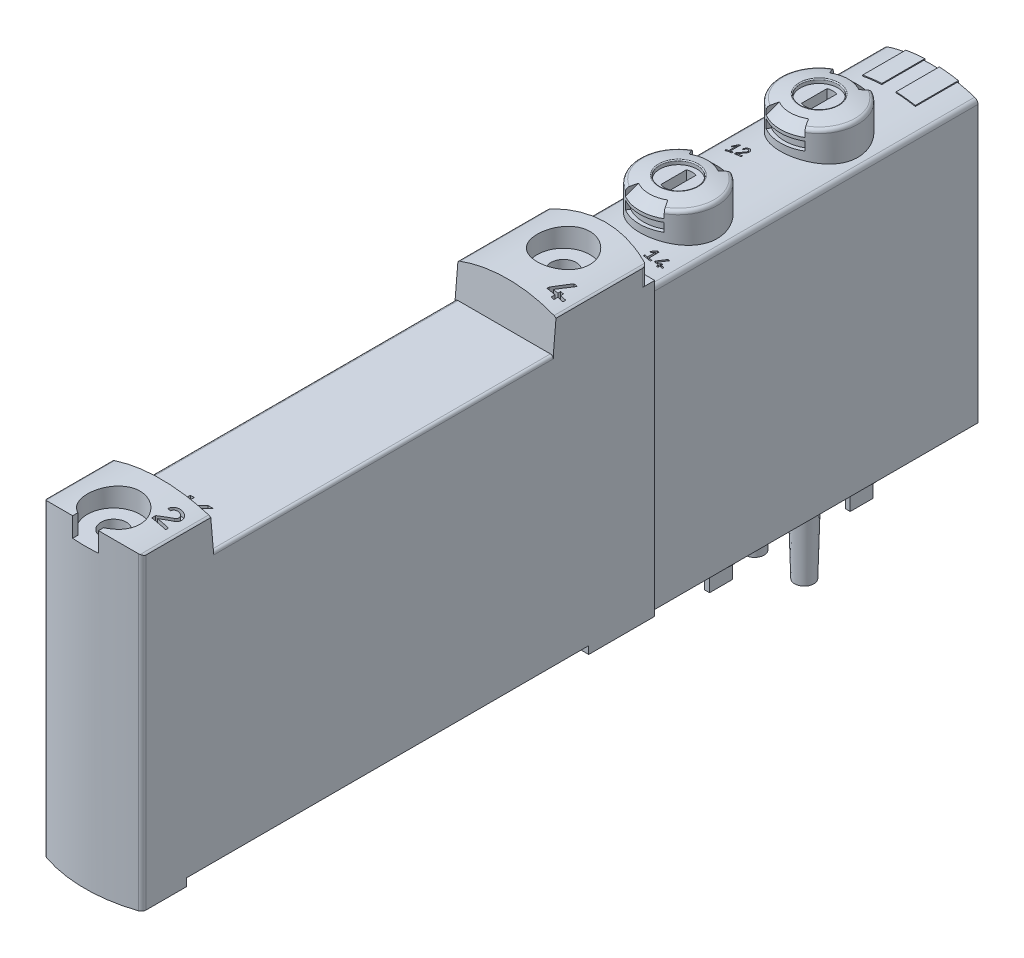
SolidWorks part; units mm, degrees
ref_plane "Front Plane" through (0, 0, 0) normal (0, 0, 1) x (1, 0, 0)
ref_plane "Top Plane" through (0, 0, 0) normal (0, 1, 0) x (1, 0, 0)
ref_plane "Right Plane" through (0, 0, 0) normal (1, 0, 0) x (0, 0, -1)
ref_plane "Plane1" through (0, 0, -23.2) normal (0, 0, 1) x (1, 0, 0)
sketch "Sketch1" plane through (0, 0, -23.2) normal (0, 0, 1) x (1, 0, 0)
  line L0 (-4.9, 29.2163) -> (-4.9, 0)
  line L1 (-4.9, 0) -> (4.9, 0)
  line L2 (4.9, 0) -> (4.9, 29.2163)
  arc A0 (4.9, 29.2163) -> (4.5517, 29.6927) centre (4.4, 29.2163) ccw
  arc A1 (4.5517, 29.6927) -> (-4.5517, 29.6927) centre (0, 15.4) ccw
  arc A2 (-4.5517, 29.6927) -> (-4.9, 29.2163) centre (-4.4, 29.2163) ccw
extrude "Boss-Extrude1" add sketch "Sketch1" along normal blind 34
ref_plane "Plane2" through (0, 0, 0) normal (1, 0, 0) x (0, 0, -1)
sketch "Sketch2" plane through (0, 0, 0) normal (1, 0, 0) x (0, 0, -1)
  line L0 (-10.88, 0.4) -> (-10.88, 0)
  line L1 (-10.88, 0) -> (23.22, 0)
  line L2 (23.22, 0) -> (23.22, 0.4)
  line L3 (23.22, 0.4) -> (-10.88, 0.4)
extrude "Cut-Extrude1" cut sketch "Sketch2" against normal blind 6 and the other way blind 6
ref_plane "Plane3" through (0, 0, 0) normal (0, 1, 0) x (1, 0, 0)
sketch "Sketch3" plane through (0, 0, 0) normal (0, 1, 0) x (1, 0, 0)
  line L0 (-3.15, 2.4653) -> (-3.15, -2.4653)
  line L1 (3.15, -2.4653) -> (3.15, 2.4653)
  arc A0 (-3.15, -2.4653) -> (3.15, -2.4653) centre (0, 0) ccw
  arc A1 (3.15, 2.4653) -> (-3.15, 2.4653) centre (0, 0) ccw
extrude "Cut-Extrude2" cut sketch "Sketch3" along normal blind 1.9
ref_plane "Plane4" through (0, 0, 0) normal (0, 1, 0) x (1, 0, 0)
sketch "Sketch4" plane through (0, 0, 0) normal (0, 1, 0) x (1, 0, 0)
  line L0 (-3.15, 17.1653) -> (-3.15, 12.2347)
  line L1 (3.15, 12.2347) -> (3.15, 17.1653)
  arc A0 (-3.15, 12.2347) -> (3.15, 12.2347) centre (0, 14.7) ccw
  arc A1 (3.15, 17.1653) -> (-3.15, 17.1653) centre (0, 14.7) ccw
extrude "Cut-Extrude3" cut sketch "Sketch4" along normal blind 1.9
ref_plane "Plane5" through (0, 0, 0) normal (1, 0, 0) x (0, 0, -1)
sketch "Sketch5" plane through (0, 0, 0) normal (1, 0, 0) x (0, 0, -1)
  line L0 (0, 2.1) -> (3.05, 2.1)
  line L1 (3.05, 2.1) -> (3.05, 1.1)
  line L2 (3.05, 1.1) -> (2.25, 1.1)
  line L3 (2.25, 1.1) -> (2.25, -1.4)
  line L4 (2.25, -1.4) -> (2.65, -1.4)
  line L5 (2.65, -1.4) -> (2.65, -1.72)
  line L6 (2.65, -1.72) -> (2.4306, -2.1)
  line L7 (2.4306, -2.1) -> (0, -2.1)
  line L8 (0, -2.1) -> (0, 2.1)
  line L9 (0, -2.1) -> (0, 2.1) construction
revolve "Revolve1" add sketch "Sketch5" angle 360 about L9 reverse direction yes
ref_plane "Plane6" through (0, 0, 0) normal (1, 0, 0) x (0, 0, -1)
sketch "Sketch6" plane through (0, 0, 0) normal (1, 0, 0) x (0, 0, -1)
  line L0 (14.7, 2.1) -> (17.75, 2.1)
  line L1 (17.75, 2.1) -> (17.75, 1.1)
  line L2 (17.75, 1.1) -> (16.95, 1.1)
  line L3 (16.95, 1.1) -> (16.95, -1.4)
  line L4 (16.95, -1.4) -> (17.35, -1.4)
  line L5 (17.35, -1.4) -> (17.35, -1.72)
  line L6 (17.35, -1.72) -> (17.1306, -2.1)
  line L7 (17.1306, -2.1) -> (14.7, -2.1)
  line L8 (14.7, -2.1) -> (14.7, 2.1)
  line L9 (14.7, -2.1) -> (14.7, 2.1) construction
revolve "Revolve2" add sketch "Sketch6" angle 360 about L9 reverse direction yes
ref_plane "Plane7" through (0, 0, -7.35) normal (0, 0, 1) x (1, 0, 0)
sketch "Sketch7" plane through (0, 0, -7.35) normal (0, 0, 1) x (1, 0, 0)
  line L0 (2.6, 0.4) -> (3.8, 0.4)
  line L1 (3.8, 0.4) -> (3.6, -6.9)
  line L2 (2.6, -7.0623) -> (2.6, 0.4)
  line L3 (2.6, -7.0623) -> (2.6, 0.4) construction
  arc A0 (3.6, -6.9) -> (2.6, -7.0623) centre (2.6, -3.9) cw
revolve "Revolve3" add sketch "Sketch7" angle 360 about L3 reverse direction yes
ref_plane "Plane8" through (0, 0, -7.35) normal (0, 0, 1) x (1, 0, 0)
sketch "Sketch8" plane through (0, 0, -7.35) normal (0, 0, 1) x (1, 0, 0)
  line L0 (-2.6, 0.4) -> (-1.4, 0.4)
  line L1 (-1.4, 0.4) -> (-1.6, -6.9)
  line L2 (-2.6, -7.0623) -> (-2.6, 0.4)
  line L3 (-2.6, -7.0623) -> (-2.6, 0.4) construction
  arc A0 (-1.6, -6.9) -> (-2.6, -7.0623) centre (-2.6, -3.9) cw
revolve "Revolve4" add sketch "Sketch8" angle 360 about L3 reverse direction yes
ref_plane "Plane9" through (0, -2.1, 0) normal (0, -1, 0) x (-1, 0, 0)
sketch "Sketch9" plane through (0, -2.1, 0) normal (0, -1, 0) x (-1, 0, 0)
  line L0 (-1.25, -1.2) -> (-0.75, -1.2)
  line L1 (-0.75, -1.2) -> (-0.75, 1.2)
  line L2 (-0.75, 1.2) -> (-1.25, 1.2)
  line L3 (-1.25, 1.2) -> (-1.25, -1.2)
extrude "Boss-Extrude2" add sketch "Sketch9" along normal blind 2.5
ref_plane "Plane10" through (0, -2.1, 0) normal (0, -1, 0) x (-1, 0, 0)
sketch "Sketch10" plane through (0, -2.1, 0) normal (0, -1, 0) x (-1, 0, 0)
  line L0 (0.75, -1.2) -> (1.25, -1.2)
  line L1 (1.25, -1.2) -> (1.25, 1.2)
  line L2 (1.25, 1.2) -> (0.75, 1.2)
  line L3 (0.75, 1.2) -> (0.75, -1.2)
extrude "Boss-Extrude3" add sketch "Sketch10" along normal blind 2.5
ref_plane "Plane11" through (0, -2.1, 0) normal (0, -1, 0) x (-1, 0, 0)
sketch "Sketch11" plane through (0, -2.1, 0) normal (0, -1, 0) x (-1, 0, 0)
  line L0 (-1.25, 13.5) -> (-0.75, 13.5)
  line L1 (-0.75, 13.5) -> (-0.75, 15.9)
  line L2 (-0.75, 15.9) -> (-1.25, 15.9)
  line L3 (-1.25, 15.9) -> (-1.25, 13.5)
extrude "Boss-Extrude4" add sketch "Sketch11" along normal blind 2.5
ref_plane "Plane12" through (0, -2.1, 0) normal (0, -1, 0) x (-1, 0, 0)
sketch "Sketch12" plane through (0, -2.1, 0) normal (0, -1, 0) x (-1, 0, 0)
  line L0 (0.75, 13.5) -> (1.25, 13.5)
  line L1 (1.25, 13.5) -> (1.25, 15.9)
  line L2 (1.25, 15.9) -> (0.75, 15.9)
  line L3 (0.75, 15.9) -> (0.75, 13.5)
extrude "Boss-Extrude5" add sketch "Sketch12" along normal blind 2.5
ref_plane "Plane13" through (0, 0, 0) normal (1, 0, 0) x (0, 0, -1)
sketch "Sketch13" plane through (0, 0, 0) normal (1, 0, 0) x (0, 0, -1)
  line L0 (-3.2, 33.13) -> (-1.25, 33.13)
  line L1 (-1.25, 33.13) -> (-1.25, 33.4583)
  line L2 (0.85, 32.8364) -> (0.85, 28.4)
  line L3 (0.85, 28.4) -> (-3.2, 28.4)
  line L4 (-3.2, 28.4) -> (-3.2, 33.13)
  line L5 (-3.2, 28.4) -> (-3.2, 33.7) construction
  arc A0 (-1.25, 33.4583) -> (-1.1362, 33.5574) centre (-1.15, 33.4583) cw
  arc A1 (-1.1362, 33.5574) -> (0.55, 33.2237) centre (-3.2, 18.7) cw
  arc A2 (0.55, 33.2237) -> (0.85, 32.8364) centre (0.45, 32.8364) cw
revolve "Revolve5" add sketch "Sketch13" angle 360 about L5 reverse direction yes
ref_plane "Plane14" through (0, 0, 0) normal (1, 0, 0) x (0, 0, -1)
sketch "Sketch14" plane through (0, 0, 0) normal (1, 0, 0) x (0, 0, -1)
  line L0 (11.5, 33.13) -> (13.45, 33.13)
  line L1 (13.45, 33.13) -> (13.45, 33.4583)
  line L2 (15.55, 32.8364) -> (15.55, 28.4)
  line L3 (15.55, 28.4) -> (11.5, 28.4)
  line L4 (11.5, 28.4) -> (11.5, 33.13)
  line L5 (11.5, 28.4) -> (11.5, 33.7) construction
  arc A0 (13.45, 33.4583) -> (13.5638, 33.5574) centre (13.55, 33.4583) cw
  arc A1 (13.5638, 33.5574) -> (15.25, 33.2237) centre (11.5, 18.7) cw
  arc A2 (15.25, 33.2237) -> (15.55, 32.8364) centre (15.15, 32.8364) cw
revolve "Revolve6" add sketch "Sketch14" angle 360 about L5 reverse direction yes
ref_plane "Plane15" through (0, 0, 0) normal (1, 0, 0) x (0, 0, -1)
sketch "Sketch15" plane through (0, 0, 0) normal (1, 0, 0) x (0, 0, -1)
  line L0 (-0.47, 33.7) -> (0.9, 32.33)
  line L1 (0.9, 32.33) -> (0.9, 32.05)
  line L2 (0.9, 32.05) -> (0.45, 32.05)
  line L3 (0.45, 32.05) -> (0.45, 31.15)
  line L4 (0.45, 31.15) -> (0.9, 31.15)
  line L5 (0.9, 31.15) -> (0.9, 30.5)
  line L6 (0.9, 30.5) -> (1.3, 30.5)
  line L7 (1.3, 30.5) -> (1.3, 33.7)
  line L8 (1.3, 33.7) -> (-0.47, 33.7)
  line L9 (-3.2, 30.5) -> (-3.2, 33.7) construction
revolve "Cut-Revolve1" cut sketch "Sketch15" angle 30 about L9 other way angle 30 reverse direction yes
ref_plane "Plane16" through (0, 0, 0) normal (1, 0, 0) x (0, 0, -1)
sketch "Sketch16" plane through (0, 0, 0) normal (1, 0, 0) x (0, 0, -1)
  line L0 (-7.7, 30.5) -> (-7.3, 30.5)
  line L1 (-7.3, 30.5) -> (-7.3, 31.15)
  line L2 (-7.3, 31.15) -> (-6.85, 31.15)
  line L3 (-6.85, 31.15) -> (-6.85, 32.05)
  line L4 (-6.85, 32.05) -> (-7.3, 32.05)
  line L5 (-7.3, 32.05) -> (-7.3, 32.33)
  line L6 (-7.3, 32.33) -> (-5.93, 33.7)
  line L7 (-5.93, 33.7) -> (-7.7, 33.7)
  line L8 (-7.7, 33.7) -> (-7.7, 30.5)
  line L9 (-3.2, 33.7) -> (-3.2, 30.5) construction
revolve "Cut-Revolve2" cut sketch "Sketch16" angle 30 about L9 other way angle 30 reverse direction yes
ref_plane "Plane17" through (0, 33.13, 0) normal (0, 1, 0) x (1, 0, 0)
sketch "Sketch17" plane through (0, 33.13, 0) normal (0, 1, 0) x (1, 0, 0)
  line L0 (0.5, -4.5344) -> (0.5, -1.8656)
  line L1 (-0.5, -1.8656) -> (-0.5, -4.5344)
  arc A0 (-0.5, -4.5344) -> (0.5, -4.5344) centre (0, -3.2) ccw
  arc A1 (0.5, -1.8656) -> (-0.5, -1.8656) centre (0, -3.2) ccw
extrude "Cut-Extrude4" cut sketch "Sketch17" against normal blind 1.7
ref_plane "Plane18" through (0, 0, 0) normal (1, 0, 0) x (0, 0, -1)
sketch "Sketch18" plane through (0, 0, 0) normal (1, 0, 0) x (0, 0, -1)
  line L0 (14.23, 33.7) -> (15.6, 32.33)
  line L1 (15.6, 32.33) -> (15.6, 32.05)
  line L2 (15.6, 32.05) -> (15.15, 32.05)
  line L3 (15.15, 32.05) -> (15.15, 31.15)
  line L4 (15.15, 31.15) -> (15.6, 31.15)
  line L5 (15.6, 31.15) -> (15.6, 30.5)
  line L6 (15.6, 30.5) -> (16, 30.5)
  line L7 (16, 30.5) -> (16, 33.7)
  line L8 (16, 33.7) -> (14.23, 33.7)
  line L9 (11.5, 30.5) -> (11.5, 33.7) construction
revolve "Cut-Revolve3" cut sketch "Sketch18" angle 30 about L9 other way angle 30 reverse direction yes
ref_plane "Plane19" through (0, 0, 0) normal (1, 0, 0) x (0, 0, -1)
sketch "Sketch19" plane through (0, 0, 0) normal (1, 0, 0) x (0, 0, -1)
  line L0 (7, 30.5) -> (7.4, 30.5)
  line L1 (7.4, 30.5) -> (7.4, 31.15)
  line L2 (7.4, 31.15) -> (7.85, 31.15)
  line L3 (7.85, 31.15) -> (7.85, 32.05)
  line L4 (7.85, 32.05) -> (7.4, 32.05)
  line L5 (7.4, 32.05) -> (7.4, 32.33)
  line L6 (7.4, 32.33) -> (8.77, 33.7)
  line L7 (8.77, 33.7) -> (7, 33.7)
  line L8 (7, 33.7) -> (7, 30.5)
  line L9 (11.5, 33.7) -> (11.5, 30.5) construction
revolve "Cut-Revolve4" cut sketch "Sketch19" angle 30 about L9 other way angle 30 reverse direction yes
ref_plane "Plane20" through (0, 33.13, 0) normal (0, 1, 0) x (1, 0, 0)
sketch "Sketch20" plane through (0, 33.13, 0) normal (0, 1, 0) x (1, 0, 0)
  line L0 (0.5, 10.1656) -> (0.5, 12.8344)
  line L1 (-0.5, 12.8344) -> (-0.5, 10.1656)
  arc A0 (-0.5, 10.1656) -> (0.5, 10.1656) centre (0, 11.5) ccw
  arc A1 (0.5, 12.8344) -> (-0.5, 12.8344) centre (0, 11.5) ccw
extrude "Cut-Extrude5" cut sketch "Sketch20" against normal blind 1.7
ref_plane "Plane21" through (0, 0, -23.3) normal (0, 0, 1) x (1, 0, 0)
sketch "Sketch21" plane through (0, 0, -23.3) normal (0, 0, 1) x (1, 0, 0)
  line L0 (0.75, 30.4814) -> (0.75, 27)
  line L1 (0.75, 27) -> (2.75, 27)
  line L2 (2.75, 27) -> (2.75, 30.2475)
  arc A0 (2.75, 30.2475) -> (0.75, 30.4814) centre (0, 15.4) ccw
extrude "Boss-Extrude6" add sketch "Sketch21" along normal blind 4.5
ref_plane "Plane22" through (0, 0, -23.3) normal (0, 0, 1) x (1, 0, 0)
sketch "Sketch22" plane through (0, 0, -23.3) normal (0, 0, 1) x (1, 0, 0)
  line L0 (-2.75, 30.2475) -> (-2.75, 27)
  line L1 (-2.75, 27) -> (-0.75, 27)
  line L2 (-0.75, 27) -> (-0.75, 30.4814)
  arc A0 (-0.75, 30.4814) -> (-2.75, 30.2475) centre (0, 15.4) ccw
extrude "Boss-Extrude7" add sketch "Sketch22" along normal blind 4.5
ref_plane "Plane23" through (0, 0, 0) normal (0, 1, 0) x (1, 0, 0)
sketch "Sketch23" plane through (0, 0, 0) normal (0, 1, 0) x (1, 0, 0)
  line L0 (5.125, -63.9426) -> (5.125, -10.8)
  line L1 (5.125, -10.8) -> (-5.125, -10.8)
  line L2 (-5.125, -10.8) -> (-5.125, -63.9426)
  arc A0 (-5.125, -63.9426) -> (-4.7845, -64.4165) centre (-4.625, -63.9426) ccw
  arc A1 (-4.7845, -64.4165) -> (4.7845, -64.4165) centre (0, -50.2) ccw
  arc A2 (4.7845, -64.4165) -> (5.125, -63.9426) centre (4.625, -63.9426) ccw
extrude "Boss-Extrude8" add sketch "Sketch23" along normal blind 33.1
ref_plane "Plane24" through (0, 0, 0) normal (1, 0, 0) x (0, 0, -1)
sketch "Sketch24" plane through (0, 0, 0) normal (1, 0, 0) x (0, 0, -1)
  line L0 (-57.7749, 38.9) -> (-56.9, 28.9)
  line L1 (-56.9, 28.9) -> (-21.4, 28.9)
  line L2 (-21.4, 28.9) -> (-20.5251, 38.9)
  line L3 (-20.5251, 38.9) -> (-57.7749, 38.9)
extrude "Cut-Extrude6" cut sketch "Sketch24" against normal blind 10 and the other way blind 10
ref_plane "Plane25" through (0, 30.4, 0) normal (0, 1, 0) x (1, 0, 0)
sketch "Sketch25" plane through (0, 30.4, 0) normal (0, 1, 0) x (1, 0, 0)
  line L0 (-5.125, -8.8) -> (-5.125, -12.0574)
  line L1 (5.125, -12.0574) -> (5.125, -8.8)
  line L2 (5.125, -8.8) -> (-5.125, -8.8)
  arc A0 (-5.125, -12.0574) -> (-4.7845, -11.5835) centre (-4.625, -12.0574) cw
  arc A1 (-4.7845, -11.5835) -> (4.7845, -11.5835) centre (0, -25.8) cw
  arc A2 (4.7845, -11.5835) -> (5.125, -12.0574) centre (4.625, -12.0574) cw
extrude "Cut-Extrude7" cut sketch "Sketch25" along normal blind 10
ref_plane "Plane26" through (0, 0, 0) normal (1, 0, 0) x (0, 0, -1)
sketch "Sketch26" plane through (0, 0, 0) normal (1, 0, 0) x (0, 0, -1)
  line L0 (-59.7, -0.2) -> (-17.7, -0.2)
  line L1 (-17.7, -0.2) -> (-17.7, 0.8)
  line L2 (-17.7, 0.8) -> (-59.7, 0.8)
  line L3 (-59.7, 0.8) -> (-59.7, -0.2)
extrude "Cut-Extrude8" cut sketch "Sketch26" against normal blind 10 and the other way blind 10
ref_plane "Plane27" through (0, 0, 10.8) normal (0, 0, 1) x (1, 0, 0)
sketch "Sketch27" plane through (0, 0, 10.8) normal (0, 0, 1) x (1, 0, 0)
  line L0 (-5.25, 35.1) -> (-5.25, 31.7999)
  line L1 (5.25, 31.7999) -> (5.25, 35.1)
  line L2 (5.25, 35.1) -> (-5.25, 35.1)
  arc A0 (-5.25, 31.7999) -> (-4.9138, 32.2723) centre (-4.75, 31.7999) cw
  arc A1 (-4.9138, 32.2723) -> (4.9138, 32.2723) centre (0, 18.1) cw
  arc A2 (4.9138, 32.2723) -> (5.25, 31.7999) centre (4.75, 31.7999) cw
extrude "Cut-Extrude9" cut sketch "Sketch27" along normal blind 55
ref_plane "Plane28" through (0, 0, 21.4) normal (0, 0, 1) x (1, 0, 0)
sketch "Sketch28" plane through (0, 0, 21.4) normal (0, 0, 1) x (1, 0, 0)
  line L0 (-4.825, 28.9) -> (4.825, 28.9)
  line L1 (5.125, 28.6) -> (5.125, 33.6)
  line L2 (5.125, 33.6) -> (-5.125, 33.6)
  line L3 (-5.125, 33.6) -> (-5.125, 28.6)
  arc A0 (-5.125, 28.6) -> (-4.825, 28.9) centre (-4.825, 28.6) cw
  arc A1 (4.825, 28.9) -> (5.125, 28.6) centre (4.825, 28.6) cw
extrude "Cut-Extrude10" cut sketch "Sketch28" along normal blind 35.5
ref_plane "Plane29" through (0, 33.1, 0) normal (0, 1, 0) x (1, 0, 0)
sketch "Sketch29" plane through (0, 33.1, 0) normal (0, 1, 0) x (1, 0, 0)
  line L0 (-1.35, -64.5958) -> (-1.35, -66)
  line L1 (-1.35, -66) -> (1.35, -66)
  line L2 (1.35, -66) -> (1.35, -64.5958)
  arc A0 (1.35, -64.5958) -> (-1.35, -64.5958) centre (0, -62.2) ccw
extrude "Cut-Extrude11" cut sketch "Sketch29" against normal blind 2.1 and the other way blind 2.1
ref_plane "Plane30" through (0, 0, 0) normal (1, 0, 0) x (0, 0, -1)
sketch "Sketch30" plane through (0, 0, 0) normal (1, 0, 0) x (0, 0, -1)
  line L0 (-62.2, 31) -> (-60.875, 31)
  line L1 (-60.875, 31) -> (-60.875, 0)
  line L2 (-60.875, 0) -> (-62.2, 0)
  line L3 (-62.2, 0) -> (-62.2, 31)
  line L4 (-62.2, 0) -> (-62.2, 31) construction
revolve "Cut-Revolve5" cut sketch "Sketch30" angle 360 about L4 reverse direction yes
ref_plane "Plane31" through (0, 0, 0) normal (1, 0, 0) x (0, 0, -1)
sketch "Sketch31" plane through (0, 0, 0) normal (1, 0, 0) x (0, 0, -1)
  line L0 (-15.2, 33.2) -> (-12.45, 33.2)
  line L1 (-12.45, 33.2) -> (-12.45, 31)
  line L2 (-12.45, 31) -> (-13.875, 31)
  line L3 (-13.875, 31) -> (-13.875, 0)
  line L4 (-13.875, 0) -> (-15.2, 0)
  line L5 (-15.2, 0) -> (-15.2, 33.2)
  line L6 (-15.2, 0) -> (-15.2, 33.2) construction
revolve "Cut-Revolve6" cut sketch "Sketch31" angle 360 about L6 reverse direction yes
ref_plane "Plane32" through (0, 0, 0) normal (1, 0, 0) x (0, 0, -1)
sketch "Sketch32" plane through (0, 0, 0) normal (1, 0, 0) x (0, 0, -1)
  line L0 (-40.2, 9.8) -> (-38.1, 9.8)
  line L1 (-38.1, 9.8) -> (-38.1, 1.8)
  line L2 (-38.1, 1.8) -> (-37.4, 1.8)
  line L3 (-37.4, 1.8) -> (-37.4, 0.8)
  line L4 (-37.4, 0.8) -> (-40.2, 0.8)
  line L5 (-40.2, 0.8) -> (-40.2, 9.8)
  line L6 (-40.2, 0.8) -> (-40.2, 9.8) construction
revolve "Cut-Revolve7" cut sketch "Sketch32" angle 360 about L6 reverse direction yes
ref_plane "Plane33" through (-1.55, 0, 0) normal (1, 0, 0) x (0, 0, -1)
sketch "Sketch33" plane through (-1.55, 0, 0) normal (1, 0, 0) x (0, 0, -1)
  line L0 (-29.1, 9.8) -> (-27, 9.8)
  line L1 (-27, 9.8) -> (-27, 1.8)
  line L2 (-27, 1.8) -> (-26.3, 1.8)
  line L3 (-26.3, 1.8) -> (-26.3, 0.8)
  line L4 (-26.3, 0.8) -> (-29.1, 0.8)
  line L5 (-29.1, 0.8) -> (-29.1, 9.8)
  line L6 (-29.1, 0.8) -> (-29.1, 9.8) construction
revolve "Cut-Revolve8" cut sketch "Sketch33" angle 360 about L6 reverse direction yes
ref_plane "Plane34" through (-1.55, 0, 0) normal (1, 0, 0) x (0, 0, -1)
sketch "Sketch34" plane through (-1.55, 0, 0) normal (1, 0, 0) x (0, 0, -1)
  line L0 (-46.1, 9.8) -> (-44, 9.8)
  line L1 (-44, 9.8) -> (-44, 1.8)
  line L2 (-44, 1.8) -> (-43.3, 1.8)
  line L3 (-43.3, 1.8) -> (-43.3, 0.8)
  line L4 (-43.3, 0.8) -> (-46.1, 0.8)
  line L5 (-46.1, 0.8) -> (-46.1, 9.8)
  line L6 (-46.1, 0.8) -> (-46.1, 9.8) construction
revolve "Cut-Revolve9" cut sketch "Sketch34" angle 360 about L6 reverse direction yes
ref_plane "Plane35" through (1.55, 0, 0) normal (1, 0, 0) x (0, 0, -1)
sketch "Sketch35" plane through (1.55, 0, 0) normal (1, 0, 0) x (0, 0, -1)
  line L0 (-34.3, 9.8) -> (-32.2, 9.8)
  line L1 (-32.2, 9.8) -> (-32.2, 1.8)
  line L2 (-32.2, 1.8) -> (-31.5, 1.8)
  line L3 (-31.5, 1.8) -> (-31.5, 0.8)
  line L4 (-31.5, 0.8) -> (-34.3, 0.8)
  line L5 (-34.3, 0.8) -> (-34.3, 9.8)
  line L6 (-34.3, 0.8) -> (-34.3, 9.8) construction
revolve "Cut-Revolve10" cut sketch "Sketch35" angle 360 about L6 reverse direction yes
ref_plane "Plane36" through (1.55, 0, 0) normal (1, 0, 0) x (0, 0, -1)
sketch "Sketch36" plane through (1.55, 0, 0) normal (1, 0, 0) x (0, 0, -1)
  line L0 (-51.3, 9.8) -> (-49.2, 9.8)
  line L1 (-49.2, 9.8) -> (-49.2, 1.8)
  line L2 (-49.2, 1.8) -> (-48.5, 1.8)
  line L3 (-48.5, 1.8) -> (-48.5, 0.8)
  line L4 (-48.5, 0.8) -> (-51.3, 0.8)
  line L5 (-51.3, 0.8) -> (-51.3, 9.8)
  line L6 (-51.3, 0.8) -> (-51.3, 9.8) construction
revolve "Cut-Revolve11" cut sketch "Sketch36" angle 360 about L6 reverse direction yes
ref_plane "Plane37" through (0, 33.1, 0) normal (0, 1, 0) x (1, 0, 0)
sketch "Sketch37" plane through (0, 33.1, 0) normal (0, 1, 0) x (1, 0, 0)
  line L0 (-3.3985, 5.738) -> (-3.2978, 5.6676)
  line L1 (-3.2978, 5.6676) -> (-3.075, 5.9858)
  line L2 (-3.075, 5.9858) -> (-3.075, 5.15)
  line L3 (-3.075, 5.15) -> (-3.375, 5.15)
  line L4 (-3.375, 5.15) -> (-3.375, 5)
  line L5 (-3.375, 5) -> (-2.625, 5)
  line L6 (-2.625, 5) -> (-2.625, 5.15)
  line L7 (-2.625, 5.15) -> (-2.925, 5.15)
  line L8 (-2.925, 5.15) -> (-2.925, 6.2)
  line L9 (-2.925, 6.2) -> (-3.075, 6.2)
  line L10 (-3.075, 6.2) -> (-3.3985, 5.738)
extrude "Cut-Extrude12" cut sketch "Sketch37" against normal blind 3.5 and the other way blind 3.5
ref_plane "Plane38" through (0, 33.1, 0) normal (0, 1, 0) x (1, 0, 0)
sketch "Sketch38" plane through (0, 33.1, 0) normal (0, 1, 0) x (1, 0, 0)
  line L0 (-2.3625, 5.8375) -> (-2.2125, 5.8375)
  line L1 (-1.8546, 5.6826) -> (-2.3625, 5.2057)
  line L2 (-2.3625, 5.2057) -> (-2.3625, 5)
  line L3 (-2.3625, 5) -> (-1.6375, 5)
  line L4 (-1.6375, 5) -> (-1.6375, 5.15)
  line L5 (-1.6375, 5.15) -> (-2.2027, 5.15)
  line L6 (-2.2027, 5.15) -> (-1.7519, 5.5732)
  arc A0 (-2.2125, 5.8375) -> (-1.8546, 5.6826) centre (-2, 5.8375) cw
  arc A1 (-1.7519, 5.5732) -> (-2.3625, 5.8375) centre (-2, 5.8375) ccw
extrude "Cut-Extrude13" cut sketch "Sketch38" against normal blind 3.5 and the other way blind 3.5
ref_plane "Plane39" through (0, 33.1, 0) normal (0, 1, 0) x (1, 0, 0)
sketch "Sketch39" plane through (0, 33.1, 0) normal (0, 1, 0) x (1, 0, 0)
  line L0 (2.1015, -8.262) -> (2.2022, -8.3324)
  line L1 (2.2022, -8.3324) -> (2.425, -8.0142)
  line L2 (2.425, -8.0142) -> (2.425, -8.85)
  line L3 (2.425, -8.85) -> (2.125, -8.85)
  line L4 (2.125, -8.85) -> (2.125, -9)
  line L5 (2.125, -9) -> (2.875, -9)
  line L6 (2.875, -9) -> (2.875, -8.85)
  line L7 (2.875, -8.85) -> (2.575, -8.85)
  line L8 (2.575, -8.85) -> (2.575, -7.8)
  line L9 (2.575, -7.8) -> (2.425, -7.8)
  line L10 (2.425, -7.8) -> (2.1015, -8.262)
extrude "Cut-Extrude14" cut sketch "Sketch39" against normal blind 3.5 and the other way blind 3.5
ref_plane "Plane40" through (0, 33.1, 0) normal (0, 1, 0) x (1, 0, 0)
sketch "Sketch40" plane through (0, 33.1, 0) normal (0, 1, 0) x (1, 0, 0)
  line L0 (3.085, -8.8) -> (3.5, -8.8)
  line L1 (3.5, -8.8) -> (3.5, -9)
  line L2 (3.5, -9) -> (3.65, -9)
  line L3 (3.65, -9) -> (3.65, -8.8)
  line L4 (3.65, -8.8) -> (3.915, -8.8)
  line L5 (3.915, -8.8) -> (3.915, -8.65)
  line L6 (3.915, -8.65) -> (3.65, -8.65)
  line L7 (3.65, -8.65) -> (3.65, -8.5)
  line L8 (3.65, -8.5) -> (3.5, -8.5)
  line L9 (3.5, -8.5) -> (3.5, -8.65)
  line L10 (3.5, -8.65) -> (3.2699, -8.65)
  line L11 (3.2699, -8.65) -> (3.6663, -7.8)
  line L12 (3.6663, -7.8) -> (3.5008, -7.8)
  line L13 (3.5008, -7.8) -> (3.085, -8.6917)
  line L14 (3.085, -8.6917) -> (3.085, -8.8)
extrude "Cut-Extrude15" cut sketch "Sketch40" against normal blind 3.5 and the other way blind 3.5
ref_plane "Plane41" through (0, 33.1, 0) normal (0, 1, 0) x (1, 0, 0)
sketch "Sketch41" plane through (0, 33.1, 0) normal (0, 1, 0) x (1, 0, 0)
  line L0 (2.67, -19.6) -> (3.5, -19.6)
  line L1 (3.5, -19.6) -> (3.5, -20)
  line L2 (3.5, -20) -> (3.8, -20)
  line L3 (3.8, -20) -> (3.8, -19.6)
  line L4 (3.8, -19.6) -> (4.33, -19.6)
  line L5 (4.33, -19.6) -> (4.33, -19.3)
  line L6 (4.33, -19.3) -> (3.8, -19.3)
  line L7 (3.8, -19.3) -> (3.8, -19)
  line L8 (3.8, -19) -> (3.5, -19)
  line L9 (3.5, -19) -> (3.5, -19.3)
  line L10 (3.5, -19.3) -> (3.0399, -19.3)
  line L11 (3.0399, -19.3) -> (3.8326, -17.6)
  line L12 (3.8326, -17.6) -> (3.5016, -17.6)
  line L13 (3.5016, -17.6) -> (2.67, -19.3834)
  line L14 (2.67, -19.3834) -> (2.67, -19.6)
extrude "Cut-Extrude16" cut sketch "Sketch41" against normal blind 1 and the other way blind 1
ref_plane "Plane42" through (0, 33.1, 0) normal (0, 1, 0) x (1, 0, 0)
sketch "Sketch42" plane through (0, 33.1, 0) normal (0, 1, 0) x (1, 0, 0)
  line L0 (2.775, -59.325) -> (3.075, -59.325)
  line L1 (3.7909, -59.6349) -> (2.775, -60.5885)
  line L2 (2.775, -60.5885) -> (2.775, -61)
  line L3 (2.775, -61) -> (4.225, -61)
  line L4 (4.225, -61) -> (4.225, -60.7)
  line L5 (4.225, -60.7) -> (3.0946, -60.7)
  line L6 (3.0946, -60.7) -> (3.9962, -59.8536)
  arc A0 (3.075, -59.325) -> (3.7909, -59.6349) centre (3.5, -59.325) cw
  arc A1 (3.9962, -59.8536) -> (2.775, -59.325) centre (3.5, -59.325) ccw
extrude "Cut-Extrude17" cut sketch "Sketch42" against normal blind 1 and the other way blind 1
ref_plane "Plane43" through (0, 33.1, 0) normal (0, 1, 0) x (1, 0, 0)
sketch "Sketch43" plane through (0, 33.1, 0) normal (0, 1, 0) x (1, 0, 0)
  line L0 (-1.2, -53) -> (-1.2, -56)
  line L1 (-1.2, -56) -> (-0.78, -56)
  line L2 (-0.78, -56) -> (-0.78, -54.95)
  line L3 (-0.78, -54.95) -> (-0.3273, -54.5041)
  line L4 (-0.3273, -54.5041) -> (0.66, -56)
  line L5 (0.66, -56) -> (1.2, -56)
  line L6 (1.2, -56) -> (0, -54.1818)
  line L7 (0, -54.1818) -> (1.2, -53)
  line L8 (1.2, -53) -> (0.66, -53)
  line L9 (0.66, -53) -> (-0.78, -54.4182)
  line L10 (-0.78, -54.4182) -> (-0.78, -53)
  line L11 (-0.78, -53) -> (-1.2, -53)
extrude "Cut-Extrude18" cut sketch "Sketch43" against normal blind 4.5 and the other way blind 4.5
